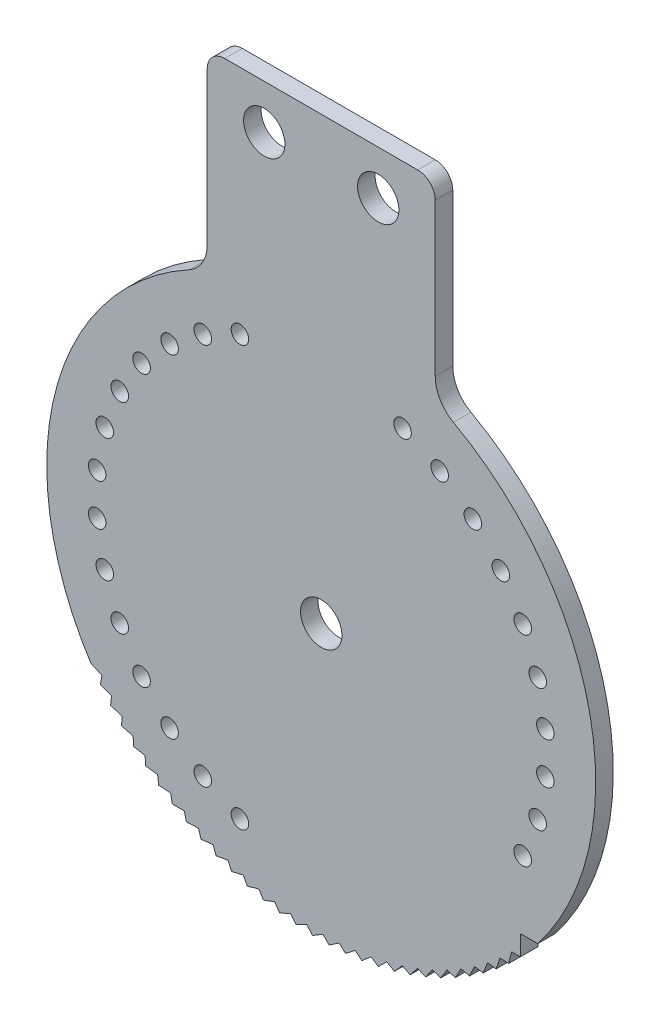
SolidWorks part; units mm, degrees
ref_plane "Front Plane" through (0, 0, 0) normal (0, 0, 1) x (1, 0, 0)
ref_plane "Top Plane" through (0, 0, 0) normal (0, 1, 0) x (1, 0, 0)
ref_plane "Right Plane" through (0, 0, 0) normal (1, 0, 0) x (0, 0, -1)
sketch "Sketch1" plane through (0, 0, 0) normal (0, 0, 1) x (1, 0, 0)
  line L0 (16.8766, 28.4861) -> (16.8766, 50.5569)
  line L1 (-13.589, 53.0969) -> (14.3366, 53.0969)
  line L2 (-21.1851, -44.1428) -> (-19.4455, -44.1554)
  line L3 (-21.1851, -44.1428) -> (-21.4191, -42.9029)
  line L4 (-23.1548, -42.7856) -> (-21.4191, -42.9029)
  line L5 (-23.1548, -42.7856) -> (-23.3139, -41.5339)
  line L6 (-25.0394, -41.3124) -> (-23.3139, -41.5339)
  line L7 (-25.0394, -41.3124) -> (-25.1229, -40.0534)
  line L8 (-26.8319, -39.7285) -> (-25.1229, -40.0534)
  line L9 (-26.8319, -39.7285) -> (-26.8395, -38.4668)
  line L10 (-28.526, -38.0397) -> (-26.8395, -38.4668)
  line L11 (-28.526, -38.0397) -> (-28.4577, -36.7797)
  line L12 (-30.1154, -36.252) -> (-28.4577, -36.7797)
  line L13 (-30.1154, -36.252) -> (-29.9714, -34.9985)
  line L14 (-31.5943, -34.372) -> (-29.9714, -34.9985)
  line L15 (-31.5943, -34.372) -> (-31.3752, -33.1294)
  line L16 (-32.9576, -32.4064) -> (-31.3752, -33.1294)
  line L17 (-19.1373, -45.379) -> (-17.4, -45.287)
  line L18 (-19.1373, -45.379) -> (-19.4455, -44.1554)
  line L19 (-17.0188, -46.4898) -> (-17.4, -45.287)
  line L20 (-17.0188, -46.4898) -> (-15.2902, -46.2935)
  line L21 (-14.8373, -47.4712) -> (-15.2902, -46.2935)
  line L22 (-14.8373, -47.4712) -> (-13.1237, -47.1713)
  line L23 (-12.6008, -48.3197) -> (-13.1237, -47.1713)
  line L24 (-12.6008, -48.3197) -> (-10.9083, -47.9172)
  line L25 (-10.3173, -49.032) -> (-10.9083, -47.9172)
  line L26 (-10.3173, -49.032) -> (-8.6521, -48.5285)
  line L27 (-7.9951, -49.6057) -> (-8.6521, -48.5285)
  line L28 (-7.9951, -49.6057) -> (-6.3632, -49.003)
  line L29 (-5.6425, -50.0387) -> (-6.3632, -49.003)
  line L30 (-5.6425, -50.0387) -> (-4.0498, -49.3389)
  line L31 (-3.2682, -50.3295) -> (-4.0498, -49.3389)
  line L32 (-3.2682, -50.3295) -> (-1.7205, -49.5351)
  line L33 (-0.8807, -50.4769) -> (-1.7205, -49.5351)
  line L34 (-0.8807, -50.4769) -> (0.6164, -49.5909)
  line L35 (1.5113, -50.4804) -> (0.6164, -49.5909)
  line L36 (1.5113, -50.4804) -> (2.9525, -49.5059)
  line L37 (3.8992, -50.34) -> (2.9525, -49.5059)
  line L38 (3.8992, -50.34) -> (5.2792, -49.2807)
  line L39 (6.2744, -50.0563) -> (5.2792, -49.2807)
  line L40 (6.2744, -50.0563) -> (7.5881, -48.9159)
  line L41 (8.6282, -49.6302) -> (7.5881, -48.9159)
  line L42 (8.6282, -49.6302) -> (9.8709, -48.4128)
  line L43 (10.9521, -49.0633) -> (9.8709, -48.4128)
  line L44 (29.1931, -38.1247) -> (27.9313, -38.1247)
  line L45 (29.1931, -38.1287) -> (29.1931, -35.2117)
  line L46 (29.1931, -35.2117) -> (31.7074, -35.2117)
  line L47 (27.4941, -39.8085) -> (27.9313, -38.1247)
  line L48 (27.4941, -39.8085) -> (26.2346, -39.7326)
  line L49 (25.6969, -41.3871) -> (26.2346, -39.7326)
  line L50 (25.6969, -41.3871) -> (24.4442, -41.2356)
  line L51 (23.808, -42.8547) -> (24.4442, -41.2356)
  line L52 (23.808, -42.8547) -> (22.5667, -42.6281)
  line L53 (21.8342, -44.2061) -> (22.5667, -42.6281)
  line L54 (19.7828, -45.4363) -> (20.6088, -43.9053)
  line L55 (21.8342, -44.2061) -> (20.6088, -43.9053)
  line L56 (19.7828, -45.4363) -> (18.5777, -45.0623)
  line L57 (17.661, -46.5409) -> (18.5777, -45.0623)
  line L58 (17.661, -46.5409) -> (16.4806, -46.0951)
  line L59 (15.4767, -47.5159) -> (16.4806, -46.0951)
  line L60 (15.4767, -47.5159) -> (14.3253, -46.9999)
  line L61 (13.2377, -48.3577) -> (12.1194, -47.7734)
  line L62 (13.2377, -48.3577) -> (14.3253, -46.9999)
  line L63 (10.9521, -49.0633) -> (12.1194, -47.7734)
  line L64 (-16.129, 28.4861) -> (-16.129, 50.5569)
  line L65 (0.3738, 28.9463) -> (0.3738, 53.0969) construction
  arc A0 (-32.9576, -32.4064) -> (-18.7623, 24.0342) centre (0.3738, -10.7841) cw
  circle A1 centre (0.3738, -10.745) radius 39.6912 construction
  circle A2 centre (-28.7881, -25.2659) radius 1.27
  circle A3 centre (-25.6234, -30.3771) radius 1.27
  circle A4 centre (-21.5733, -34.8198) radius 1.27
  circle A5 centre (-16.7759, -38.4427) radius 1.27
  circle A6 centre (-11.3945, -41.1223) radius 1.27
  circle A7 centre (29.5357, -25.2659) radius 1.27
  circle A8 centre (31.7074, -19.6602) radius 1.27
  circle A9 centre (32.8121, -13.7508) radius 1.27
  circle A10 centre (32.8121, -7.7391) radius 1.27
  circle A11 centre (31.7074, -1.8298) radius 1.27
  circle A12 centre (29.5357, 3.7759) radius 1.27
  circle A13 centre (26.371, 8.8872) radius 1.27
  circle A14 centre (22.3209, 13.3299) radius 1.27
  circle A15 centre (17.5235, 16.9527) radius 1.27
  circle A16 centre (12.142, 19.6324) radius 1.27
  circle A17 centre (-11.3945, 19.6324) radius 1.27
  circle A18 centre (-16.7759, 16.9527) radius 1.27
  circle A19 centre (-21.5733, 13.3299) radius 1.27
  circle A20 centre (-25.6234, 8.8872) radius 1.27
  circle A21 centre (-28.7881, 3.7759) radius 1.27
  circle A22 centre (-30.9598, -1.8298) radius 1.27
  circle A23 centre (-32.0645, -7.7391) radius 1.27
  circle A24 centre (-32.0645, -13.7508) radius 1.27
  circle A25 centre (-30.9598, -19.6602) radius 1.27
  circle A26 centre (0.3738, -10.745) radius 2.9925
  arc A27 (19.5099, 24.0342) -> (31.7074, -35.2117) centre (0.3738, -10.7841) cw
  circle A28 centre (-7.8776, 46.7085) radius 2.9925
  circle A30 centre (8.6252, 46.7085) radius 2.9925
  arc A31 (19.5099, 24.0342) -> (16.8766, 28.4861) centre (21.9566, 28.4861) cw
  arc A32 (-18.7623, 24.0342) -> (-16.129, 28.4861) centre (-21.209, 28.4861) ccw
  arc A33 (-13.589, 53.0969) -> (-16.129, 50.5569) centre (-13.589, 50.5569) ccw
  arc A34 (14.3366, 53.0969) -> (16.8766, 50.5569) centre (14.3366, 50.5569) cw
  dimension "D1" = 5.08
  dimension "D2" = 2.54
extrude "Boss-Extrude1" add sketch "Sketch1" along normal blind 2.54 contours A34 L1 A33 L64 A32 A0 L16 L15 L14 L13 L12 L11 L10 L9 L8 L7 L6 L5 L4 L3 L2 L18 L17 L19 L20 L21 L22 L23 L24 L25 L26 L27 L28 L29 L30 L31 L32 L33 L34 L35 L36 L37 L38 L39 L40 L41 L42 L43 L63 L61 L62 region at (0.4418, -3.539, 0)
